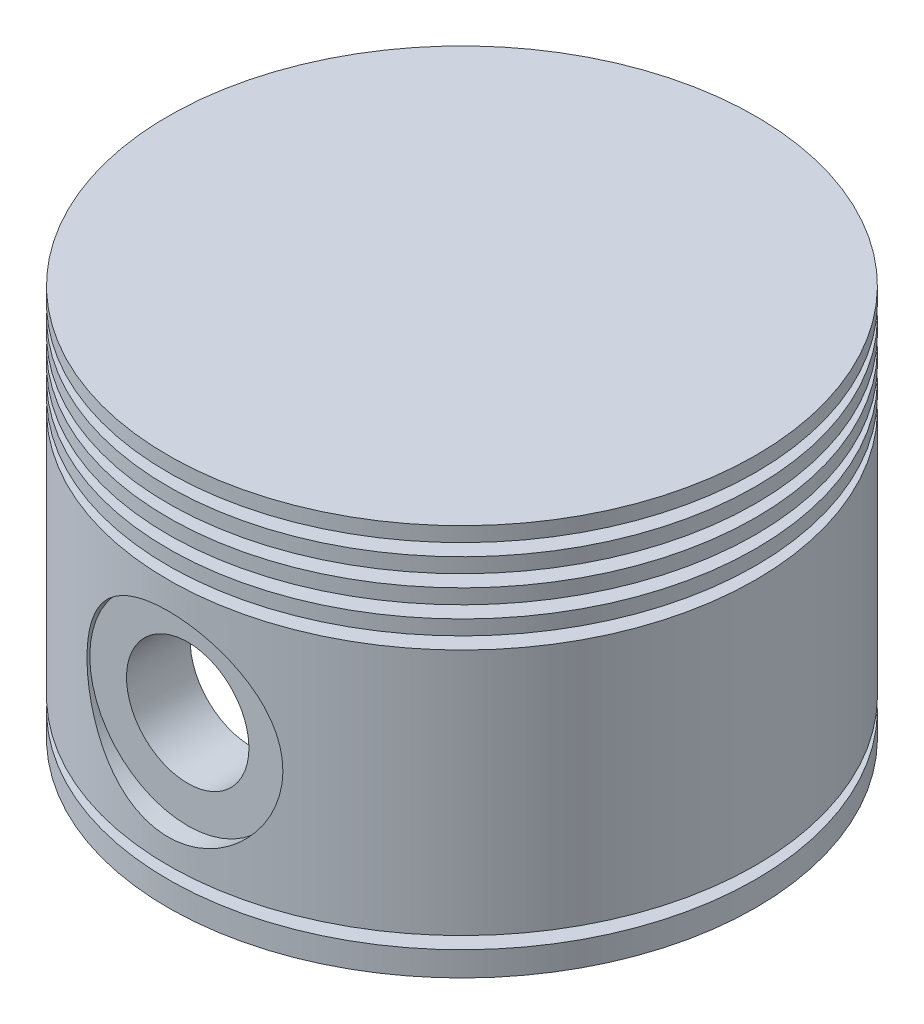
SolidWorks part; units mm, degrees
ref_plane "Front Plane" through (0, 0, 0) normal (0, 0, 1) x (1, 0, 0)
ref_plane "Top Plane" through (0, 0, 0) normal (0, 1, 0) x (1, 0, 0)
ref_plane "Right Plane" through (0, 0, 0) normal (1, 0, 0) x (0, 0, -1)
sketch "Sketch1" plane through (0, 0, 0) normal (0, 0, 1) x (1, 0, 0)
  line L1 (0, 0) -> (-30, 0)
  line L2 (0, 0) -> (0, 40) construction
  line L3 (0, 40) -> (-30, 40)
  line L4 (-30, 0) -> (-30, 40)
  line L5 (-30, 38.5) -> (-28, 38.5)
  line L6 (-30, 38.5) -> (-30, 37.25)
  line L7 (-30, 37.25) -> (-28, 37.25)
  line L8 (-28, 38.5) -> (-28, 37.25)
  line L9 (-30, 35.75) -> (-28, 35.75)
  line L10 (-30, 35.75) -> (-30, 34.5)
  line L11 (-30, 34.5) -> (-28, 34.5)
  line L12 (-28, 35.75) -> (-28, 34.5)
  line L13 (-30, 33) -> (-28, 33)
  line L14 (-30, 33) -> (-30, 31.75)
  line L15 (-30, 31.75) -> (-28, 31.75)
  line L16 (-28, 33) -> (-28, 31.75)
  line L17 (-30, 30.25) -> (-28, 30.25)
  line L18 (-30, 30.25) -> (-30, 29)
  line L19 (-30, 29) -> (-28, 29)
  line L20 (-28, 30.25) -> (-28, 29)
  line L21 (-30, 3.75) -> (-28, 3.75)
  line L22 (-30, 3.75) -> (-30, 2.5)
  line L23 (-30, 2.5) -> (-28, 2.5)
  line L24 (-28, 3.75) -> (-28, 2.5)
  dimension "D1" = 30
  dimension "D2" = 1.25
  dimension "D3" = 1.5
  dimension "D4" = 1.5
  dimension "D5" = 1.5
  dimension "D6" = 2.5
  dimension "D7" = 1.5
  dimension "D8" = 40
  dimension "D9" = 2
revolve "Revolve1" add sketch "Sketch1" angle 360 about L2 region at (-14.8526, 19.9197, 0)
sketch "Sketch2" plane through (0, 0, 0) normal (0, -1, 0) x (1, 0, 0)
  circle A2 centre (0, 0) radius 25
  circle A3 centre (0, 0) radius 25
  dimension "D1" = 5
extrude "Cut-Extrude1" cut sketch "Sketch2" against normal blind 35
ref_plane "Plane1" through (0, 0, 30) normal (0, 0, 1) x (1, 0, 0)
sketch "Sketch3" plane through (0, 0, 30) normal (0, 0, 1) x (1, 0, 0)
  line L0 (0, 16.25) -> (0, 0) construction
  circle A0 centre (0, 16.25) radius 10
  circle A1 centre (0, 16.25) radius 6.25
  dimension "D1" = 20
  dimension "D2" = 12.5
  dimension "D3" = 16.25
extrude "Cut-Extrude2" cut sketch "Sketch3" against normal blind 2
extrude "Cut-Extrude3" cut sketch "Sketch3<2>" against normal up to surface (5.7939 mm away) contours A1 region at (0, 16.25, 30) up to face at (25, 35, 0)
sketch "Sketch3<2>" plane through (0, 0, 30) normal (0, 0, 1) x (1, 0, 0) same geometry as "Sketch3"
extrude "Boss-Extrude1" add sketch "Sketch3<3>" against normal blind 6.5 from surface starting at face at (6.25, 16.25, 28)
sketch "Sketch3<3>" plane through (0, 0, 30) normal (0, 0, 1) x (1, 0, 0) same geometry as "Sketch3"
mirror "Mirror1" about plane through (0, 0, 0) normal (0, 0, 1) of "Cut-Extrude2", "Cut-Extrude3"
extrude "Boss-Extrude2" add sketch "Sketch3<4>" along normal blind 6.5 from surface starting at face at (10, 16.25, -28)
sketch "Sketch3<4>" plane through (0, 0, 30) normal (0, 0, 1) x (1, 0, 0) same geometry as "Sketch3"
equation "\"D4@Sketch1\"=\"D3@Sketch1\""
equation "\"D5@Sketch1\"=\"D3@Sketch1\""
